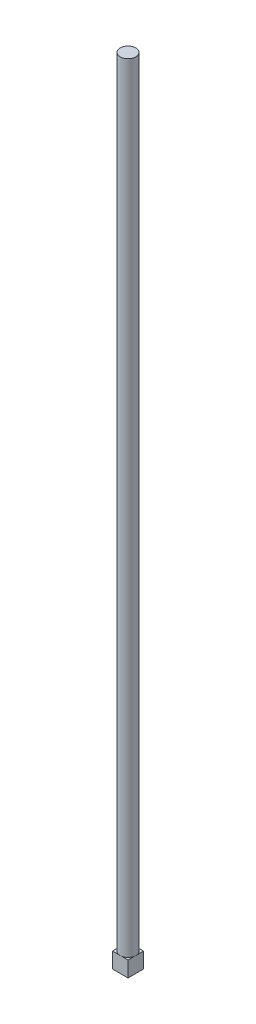
SolidWorks part; units mm, degrees
ref_plane "Front Plane" through (0, 0, 0) normal (0, 0, 1) x (1, 0, 0)
ref_plane "Top Plane" through (0, 0, 0) normal (0, 1, 0) x (1, 0, 0)
ref_plane "Right Plane" through (0, 0, 0) normal (1, 0, 0) x (0, 0, -1)
sketch "Sketch1" plane through (0, 0, 0) normal (0, 1, 0) x (1, 0, 0)
  line L1 (-12.7, 12.7) -> (12.7, 12.7)
  line L2 (-12.7, 12.7) -> (-12.7, -12.7)
  line L3 (-12.7, -12.7) -> (12.7, -12.7)
  line L4 (12.7, 12.7) -> (12.7, -12.7)
  line L5 (-12.7, 12.7) -> (12.7, -12.7) construction
  line L6 (-12.7, -12.7) -> (12.7, 12.7) construction
  circle A0 centre (0, 0) radius 12.7
  point P0 (0, 0)
  dimension "D1" = 25.4
extrude "Boss-Extrude1" add sketch "Sketch1" against normal blind 25.4 contours A0 L1 L2 | A0 L2 L3 | A0 | A0 L4 L1 | A0 L3 L4 region at (-9.8632, 0, -9.8632) region at (9.8632, 0, -9.8632) region at (0, 0, 0) region at (-9.8632, 0, 9.8632) region at (9.8632, 0, 9.8632)
extrude "Boss-Extrude2" add sketch "Sketch1<3>" along normal blind 1270 contours A0 region at (0, 0, 0)
sketch "Sketch1<3>" plane through (0, 0, 0) normal (0, 1, 0) x (1, 0, 0) same geometry as "Sketch1"
